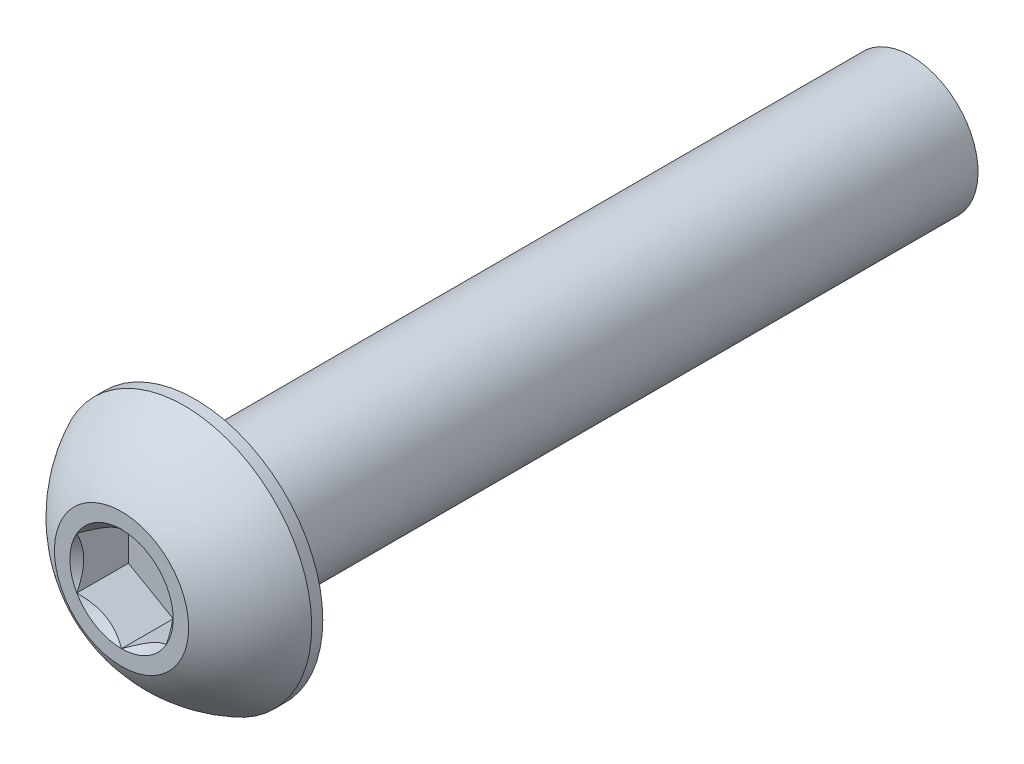
SolidWorks part; units mm, degrees
ref_plane "Front" through (0, 0, 0) normal (0, 0, 1) x (1, 0, 0)
ref_plane "Top" through (0, 0, 0) normal (0, 1, 0) x (1, 0, 0)
ref_plane "Right" through (0, 0, 0) normal (1, 0, 0) x (0, 0, -1)
sketch "Sketch1" plane through (0, 0, 0) normal (1, 0, 0) x (0, 0, -1)
  line L2 (1.65, 1.5) -> (17.65, 1.5)
  line L3 (17.65, 1.5) -> (17.65, 0)
  line L4 (17.65, 0) -> (1.65, 0)
  line L6 (1.4025, 2.85) -> (1.65, 2.85) construction
  line L7 (17.65, 1.5) -> (17.65, -1.5) construction
  line L8 (0, 0) -> (1.65, 0) construction
  line L9 (1.65, 2.85) -> (1.65, -2.85) construction
  line L11 (1.65, 1.5) -> (1.65, 0)
  line L13 (0, 1) -> (0, -1) construction
  line L14 (0, 1) -> (0, 1.5) construction
  line L15 (17.65, -1.5) -> (17.15, -1.5) construction
  arc A3 (0, 1.5) -> (1.4025, 2.85) centre (2.7948, 0) cw construction
  dimension "D1" = 0.2475
  dimension "Pitch" = 0.5
revolve "Revolve1" add sketch "Sketch1" angle 360 mid plane about L4
sketch "Sketch7" plane through (0, 0, 0) normal (1, 0, 0) x (0, 0, -1)
  line L6 (1.4025, 2.85) -> (1.65, 2.85) construction
  line L8 (0, 0) -> (1.65, 0) construction
  line L11 (1.65, 2.85) -> (1.65, -2.85) construction
  line L12 (1.4025, 2.85) -> (1.65, 2.85)
  line L13 (0, 0) -> (1.65, 0)
  line L14 (0, 1) -> (0, -1) construction
  line L15 (1.65, 2.85) -> (1.65, 0)
  line L16 (0, 1.5) -> (0, 0)
  arc A2 (1.4025, 2.85) -> (0, 1.5) centre (2.7948, 0) ccw construction
  arc A3 (1.4025, 2.85) -> (0, 1.5) centre (2.7948, 0) ccw
revolve "Revolve2" add sketch "Sketch7" angle 360 mid plane about L13
sketch "Sketch5" plane through (0, 0, 0) normal (0, 0, 1) x (1, 0, 0)
  line L1 (1, -0.5774) -> (1, 0.5774)
  line L2 (1, 0.5774) -> (0, 1.1547)
  line L3 (0, 1.1547) -> (-1, 0.5774)
  line L4 (-1, 0.5774) -> (-1, -0.5774)
  line L5 (-1, -0.5774) -> (0, -1.1547)
  line L6 (0, -1.1547) -> (1, -0.5774)
  circle A0 centre (0, 0) radius 1 construction
extrude "Cut-Extrude2" cut sketch "Sketch5" against normal blind 1.155
sketch "Sketch6" plane through (0, 0, 0) normal (0, 0, 1) x (1, 0, 0)
  circle A0 centre (0, 0) radius 1.1547
extrude "Cut-Extrude3" cut sketch "Sketch6" against normal blind 1.155 draft 45
sketch "Sketch11" plane through (0, 0, 0) normal (1, 0, 0) x (0, 0, -1)
  line L0 (1.65, -2.85) -> (1.65, 2.85)
  point P4 (1.65, 0)
split "Split1" trim tools "Sketch11" bodies to split 113 resulting bodies 119 120
sketch "Sketch10" plane through (0, 0, 0) normal (1, 0, 0) x (0, 0, -1)
  line L0 (17.65, 1.5) -> (17.65, -1.5) construction
  point P0 (16.9, -1.5)
  dimension "D1" = 0.75
sketch "Sketch3" [suppressed] plane through (0, 0, -17.65) normal (0, 0, -1) x (-1, 0, 0)
  circle A0 centre (0, 0) radius 1.5
curve "Helix/Spiral1" [suppressed] pitch 0.5 height 16.5 turns 33
sketch "Sketch2" [suppressed] plane through (0, 0, 0) normal (1, 0, 0) x (0, 0, -1)
  line L0 (17.6187, 1.5541) -> (18.1187, 1.5541) construction
  line L1 (18.1187, 1.5541) -> (17.8687, 1.1211) construction
  line L2 (17.8687, 1.1211) -> (17.6187, 1.5541) construction
  line L3 (17.8687, 1.5541) -> (17.8687, 1.5) construction
  line L4 (17.8687, 1.5) -> (17.8687, 1.1752) construction
  line L5 (17.8687, 1.1752) -> (17.8687, 1.1211) construction
  line L6 (17.8375, 1.1752) -> (17.9, 1.1752)
  line L7 (17.65, 1.5) -> (18.0875, 1.5) construction
  line L8 (17.6344, 1.5271) -> (18.1031, 1.5271)
  line L9 (17.6344, 1.5271) -> (17.8375, 1.1752)
  line L10 (18.1031, 1.5271) -> (17.9, 1.1752)
  point P10 (17.8687, 1.1752)
  point P13 (17.8687, 1.5)
  point P16 (17.8687, 1.5271)
  dimension "D1" = 0.5
  dimension "D2" = 0.0625
chamfer "Chamfer1" [suppressed] distance 0.375 angle 45
sweep "Cut-Sweep1" [suppressed] cut profiles "Sketch2" path "Helix/Spiral1"
combine bodies "Combine1" [suppressed] operation type add bodies to combine 120 114
equation "\"D3@Helix/Spiral1\" = \"Lg@Sketch1\" + \"D4@Helix/Spiral1\""
equation "\"D1@Chamfer1\" = \"D4@Helix/Spiral1\" * .75"
equation "\"D1@Cut-Extrude2\" = \"Head Ht@Sketch1\" * .7"
equation "\"D1@Sketch1\" = \"Head Ht@Sketch1\" * .15"
equation "\"D1@Sketch10\" = \"D4@Helix/Spiral1\" * 1.5"
equation "\"D1@Cut-Extrude3\" = \"D1@Cut-Extrude2\""
equation "\"D4@Helix/Spiral1\"=\"Pitch@Sketch1\""
equation "\"D1@Sketch2\"=\"Pitch@Sketch1\""
equation "\"D2@Sketch2\"=\"D1@Sketch2\"/8"
